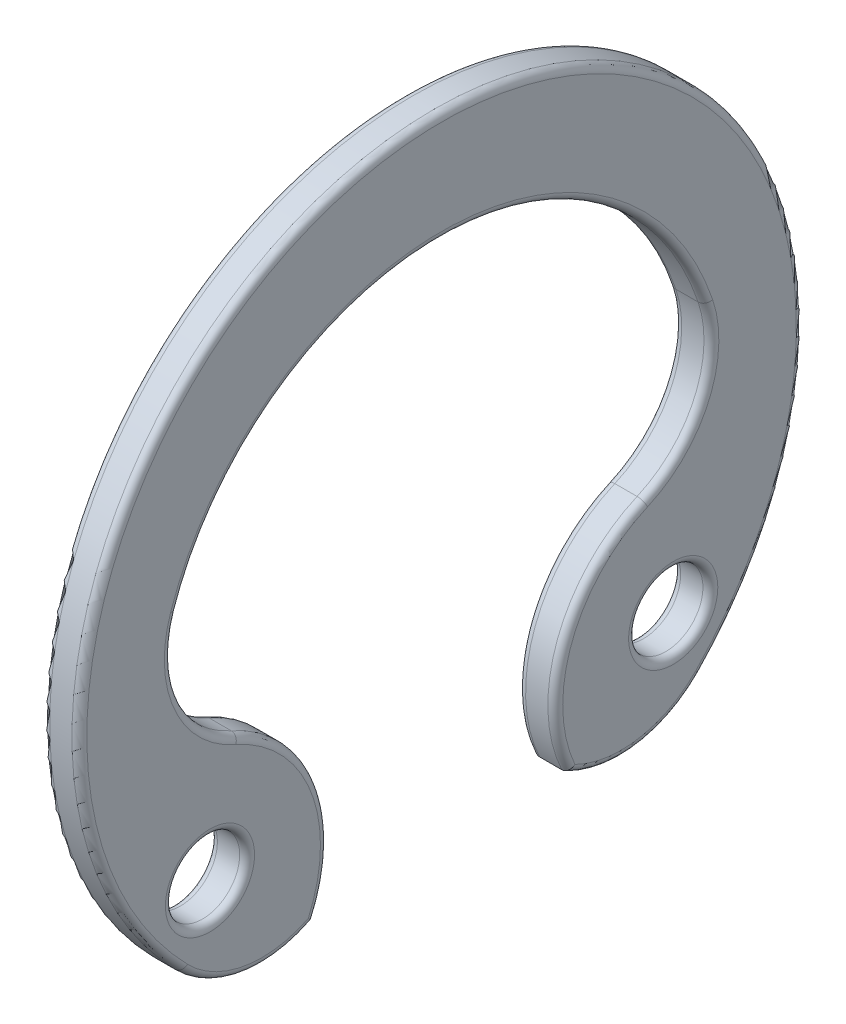
SolidWorks part; units mm, degrees
ref_plane "前视基准面" through (0, 0, 0) normal (0, 0, 1) x (1, 0, 0)
ref_plane "上视基准面" through (0, 0, 0) normal (0, 1, 0) x (1, 0, 0)
ref_plane "右视基准面" through (0, 0, 0) normal (1, 0, 0) x (0, 0, -1)
other "Configuration Table"
sketch "草图1" plane through (0, 0, 0) normal (1, 0, 0) x (0, 0, -1)
  line L0 (-12.9674, 0) -> (12.0034, 0) construction
  line L1 (0, 10.2013) -> (0, -10.2013) construction
  line L2 (3.4353, -7.367) -> (4.1205, -8.8365)
  line L3 (-3.4353, -7.367) -> (-4.1205, -8.8365)
  line L4 (0, 0) -> (3.4353, -7.367) construction
  line L5 (0, 0) -> (-3.4353, -7.367) construction
  line L6 (0, 0) -> (7.0605, -5.6765) construction
  arc A0 (4.1205, -8.8365) -> (-4.1205, -8.8365) centre (0, 0) ccw
  arc A1 (7.4338, -1.694) -> (-7.4338, -1.694) centre (0, -0.7) ccw
  arc A2 (7.4338, -1.694) -> (3.4353, -7.367) centre (7.0605, -5.6765) ccw
  circle A3 centre (6.2348, -5.0127) radius 1
  circle A4 centre (-6.2348, -5.0127) radius 1
  arc A5 (-7.4338, -1.694) -> (-3.4353, -7.367) centre (-7.0605, -5.6765) cw
  point P13 (0, 0)
  dimension "D1" = 19.5
  dimension "D2" = 15
  dimension "D5" = 8
  dimension "D6" = 2
  dimension "D3" = 0.7
  dimension "D4" = 25
  dimension "D7" = 1.6214
  dimension "D8" = 8
  dimension "D9" = 25
extrude "凸台-拉伸1" add sketch "草图1" along normal blind 1
fillet "圆角1" radius 3 4 edges at (0.5, -8.8365, -4.1205) (0.5, -8.8365, 4.1205) (0.5, -1.694, 7.4338) (0.5, -1.694, -7.4338)
fillet "圆角2" radius 0.2 20 edges at (0, -5.0127, 7.2348) (0, -5.0127, -7.2348) (0, -7.6756, 5.301) (0, -4.2611, 3.3193) (0, -0.4746, 7.0063) (0, 6.8, 0) (0, -0.4746, -7.0063) (0, -4.2611, -3.3193) (0, -7.6756, -5.301) (0, 9.75, 0) (1, -5.0127, 7.2348) (1, -0.4746, -7.0063) (1, 6.8, 0) (1, -0.4746, 7.0063) (1, -4.2611, 3.3193) (1, -7.6756, 5.301) (1, 9.75, 0) (1, -7.6756, -5.301) (1, -4.2611, -3.3193) (1, -5.0127, -7.2348)
